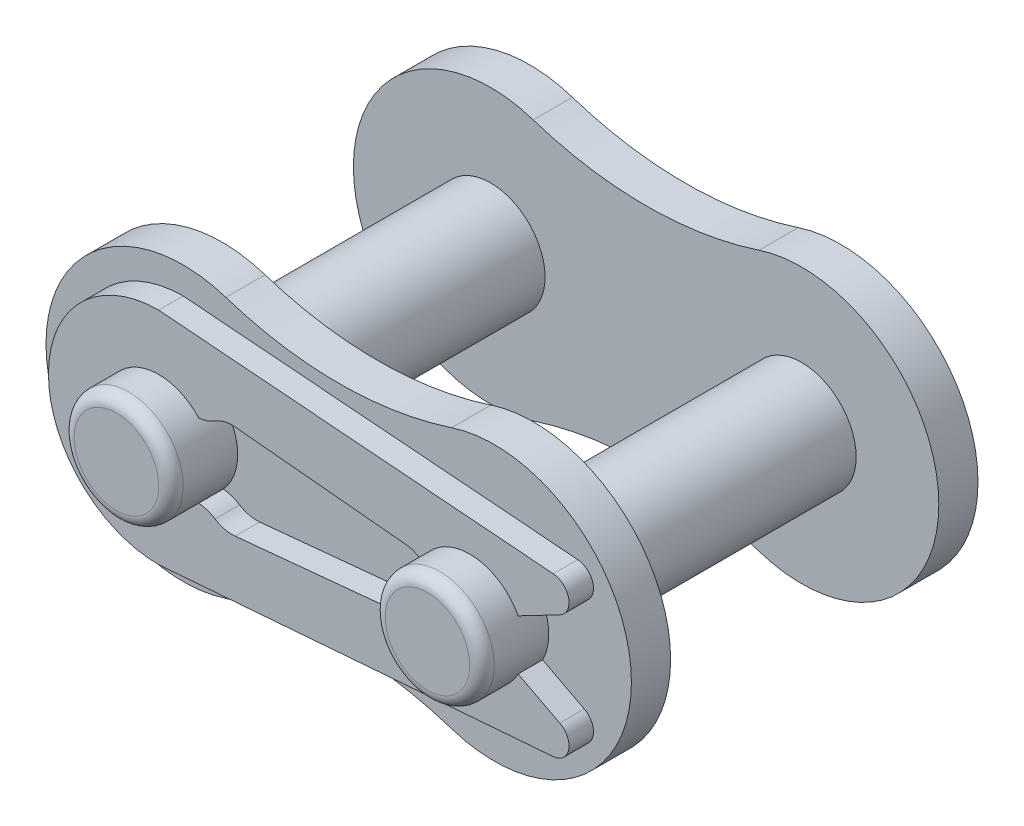
SolidWorks part; units mm, degrees
ref_plane "Front Plane" through (0, 0, 0) normal (0, 0, 1) x (1, 0, 0)
ref_plane "Top Plane" through (0, 0, 0) normal (0, 1, 0) x (1, 0, 0)
ref_plane "Right Plane" through (0, 0, 0) normal (1, 0, 0) x (0, 0, -1)
ref_axis "Axis_X" through (-19.495, 0, 0) along (1, 0, 0)
ref_axis "Axis_Y" through (0, 6.16, 0) along (0, -1, 0)
ref_axis "Axis_Z" through (0, 0, -9.31) along (0, 0, 1)
sketch "Sketch1" plane through (0, 0, 0) normal (0, 1, 0) x (1, 0, 0)
  line L0 (0, 0) -> (0, 8.4) construction
  line L1 (0, -9.8) -> (0, 8.4)
  line L2 (3.2, 7.075) -> (2.225, 7.075)
  line L3 (2.225, 7.075) -> (2.225, -9.3)
  line L4 (1.725, -9.8) -> (0, -9.8)
  arc A0 (3.2, 7.075) -> (0, 8.4) centre (0, 3.8733) ccw
  arc A1 (1.725, -9.8) -> (2.225, -9.3) centre (1.725, -9.3) ccw
  dimension "FIX_6" = 0.5
  dimension "FIX_3" = 4.45
  dimension "FIX_4" = 6.4
  dimension "FIX_1" = 8.4
  dimension "FIX_2" = 9.8
  dimension "FIX_5" = 1.325
revolve "Revolve1" add sketch "Sketch1" angle 360 about axis through (0, 0, -9.31) along (0, 0, 1)
sketch "Sketch2" plane through (0, 0, 0) normal (0, -1, 0) x (1, 0, 0)
  line L0 (-12.7, 9.8) -> (-12.7, -8.4) construction
  line L1 (-12.7, 9.8) -> (-14.425, 9.8)
  line L2 (-14.925, 9.3) -> (-14.925, -7.075)
  line L3 (-14.925, -7.075) -> (-15.9, -7.075)
  line L4 (-12.7, -8.4) -> (-12.7, 9.8)
  arc A0 (-15.9, -7.075) -> (-12.7, -8.4) centre (-12.7, -3.8733) ccw
  arc A1 (-14.925, 9.3) -> (-14.425, 9.8) centre (-14.425, 9.3) cw
  dimension "FIX_13" = 0.5
  dimension "FIX_8" = 4.45
  dimension "FIX_9" = 6.4
  dimension "FIX_10" = 1.325
  dimension "FIX_72" = 9.8
  dimension "FIX_71" = 8.4
  dimension "FIX_14" = 12.7
revolve "Revolve2" add sketch "Sketch2" angle 360 about L0
sketch "Sketch3" plane through (0, 0, -7.075) normal (0, 0, 1) x (0, 1, 0)
  line L0 (0, 0) -> (0, 12.7) construction
  line L1 (-5.6, 0) -> (5.6, 0) construction
  arc A0 (-5.3224, 1.7414) -> (5.3224, 1.7414) centre (0, 0) ccw
  arc A1 (5.3224, 10.9586) -> (-5.3224, 10.9586) centre (0, 12.7) ccw
  circle A2 centre (0, 0) radius 2.225
  circle A3 centre (0, 12.7) radius 2.225
  arc A4 (5.3224, 10.9586) -> (5.3224, 1.7414) centre (19.4076, 6.35) ccw
  arc A5 (-5.3224, 10.9586) -> (-5.3224, 1.7414) centre (-19.4076, 6.35) cw
  dimension "FIX_16" = 4.45
  dimension "FIX_17" = 14.82
  dimension "FIX_18" = 11.2
extrude "Boss-Extrude1" add sketch "Sketch3" along normal blind 1.6
mirror "Mirror1" about plane through (0, 0, 0) normal (0, 0, 1) of "Boss-Extrude1"
sketch "Sketch4" plane through (0, 0, 7.075) normal (0, 0, 1) x (1, 0, 0)
  line L0 (0, 0) -> (-12.7, 0) construction
  line L1 (-12.7, 4.5) -> (3.4076, 3.2323)
  line L2 (-12.7, -4.5) -> (3.4076, -3.2323)
  line L3 (0, 0) -> (1.9736, 1.0274) construction
  line L4 (0, 0) -> (1.9736, -1.0274) construction
  line L5 (1.9736, 1.0274) -> (3.6759, 1.9136)
  line L6 (1.9736, -1.0274) -> (3.6759, -1.9136)
  line L7 (-1.9736, -1.0274) -> (-2.2027, -1.1466)
  line L8 (-1.9736, 1.0274) -> (-2.2027, 1.1466)
  line L9 (-2.5686, 1.255) -> (-9.5754, 1.9297)
  line L10 (-2.5686, -1.255) -> (-9.5754, -1.9297)
  arc A0 (-11.0624, 1.5063) -> (-11.0624, -1.5063) centre (-12.7, 0) ccw
  arc A1 (-1.9736, -1.0274) -> (-1.9736, 1.0274) centre (0, 0) ccw
  arc A2 (-12.7, 4.5) -> (-12.7, -4.5) centre (-12.7, 0) ccw
  arc A3 (3.6759, 1.9136) -> (3.4076, 3.2323) centre (3.3527, 2.5345) ccw
  arc A4 (3.4076, -3.2323) -> (3.6759, -1.9136) centre (3.3527, -2.5345) ccw
  arc A5 (-2.2027, 1.1466) -> (-2.5686, 1.255) centre (-2.6644, 0.2596) ccw
  arc A6 (-9.5754, 1.9297) -> (-10.3964, 1.7334) centre (-9.7, 0.6357) ccw
  arc A7 (-11.0624, 1.5063) -> (-10.3964, 1.7334) centre (-11.2, 3) ccw
  arc A10 (-2.2027, -1.1466) -> (-2.5686, -1.255) centre (-2.6644, -0.2596) cw
  arc A11 (-9.5754, -1.9297) -> (-10.3964, -1.7334) centre (-9.7, -0.6357) cw
  arc A12 (-11.0624, -1.5063) -> (-10.3964, -1.7334) centre (-11.2, -3) cw
  circle M1 centre (0, 0) radius 2.225
  arc M2 (-1.7414, 5.3224) -> (-10.9586, 5.3224) centre (-6.35, 19.4076) cw
  arc M3 (-10.9586, 5.3224) -> (-10.9586, -5.3224) centre (-12.7, 0) ccw
  arc M4 (-10.9586, -5.3224) -> (-1.7414, -5.3224) centre (-6.35, -19.4076) cw
  arc M5 (-1.7414, -5.3224) -> (-1.7414, 5.3224) centre (0, 0) ccw
  circle M6 centre (-12.7, 0) radius 2.225
  dimension "FIX_20" = 4.5
  dimension "FIX_21" = 0.7
  dimension "FIX_11" = 4.45
  dimension "FIX_22" = 1
  dimension "FIX_24" = 1.5
  dimension "FIX_25" = 1.3
  dimension "FIX_23" = 5.5
  dimension "FIX_12" = 55
  dimension "FIX_19" = 9
  dimension "FIX_26" = 3
  dimension "FIX_27" = 1.5
  dimension "FIX_28" = 3
extrude "Boss-Extrude2" add sketch "Sketch4" along normal blind 1 contours M3 M2 M5 | M3 M5 M4 | A12 A7 A6 L9 A5 L8 L5 A3 L1 A2 L2 A4 L6 L7 A10 L10 A11 M6 M1 region at (-4.6643, 3.6361, 7.075)
equation "\"Factor\"= 1.082532"
